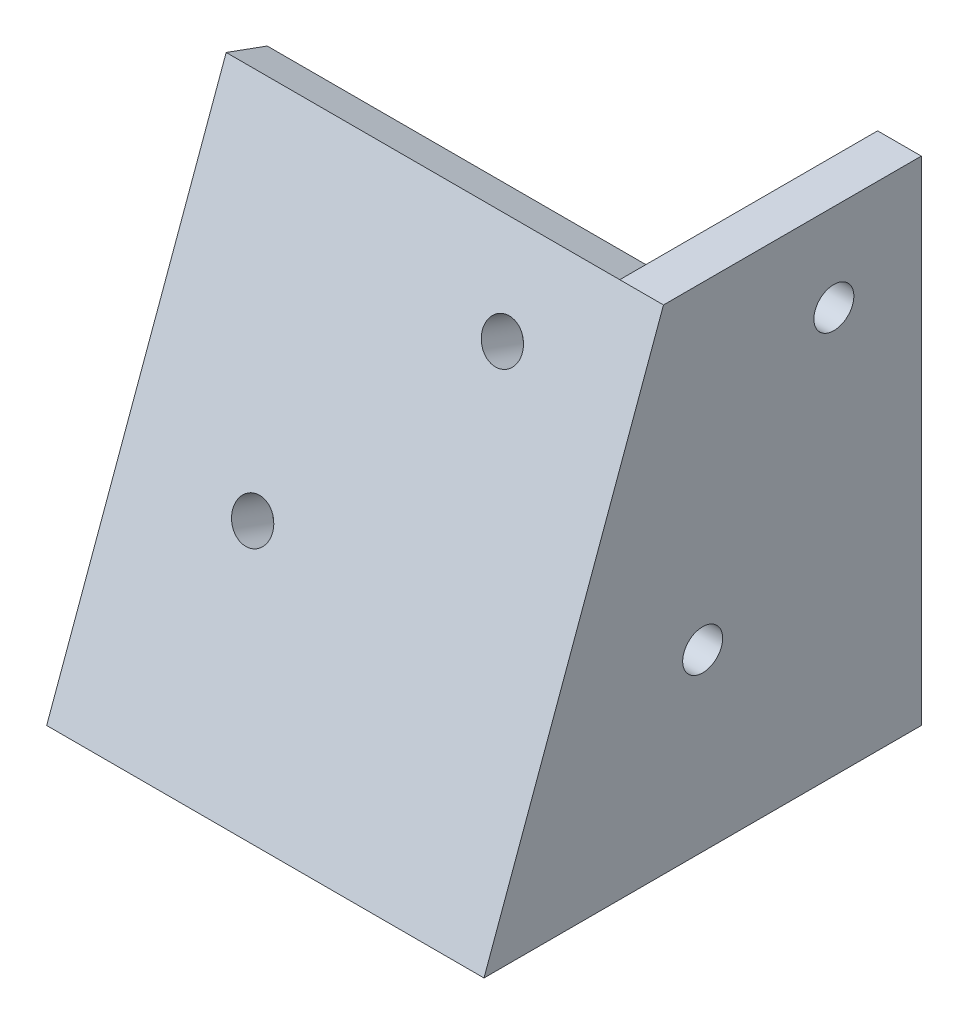
SolidWorks part; units mm, degrees
material "ABS"
ref_plane "Front Plane" through (0, 0, 0) normal (0, 0, 1) x (1, 0, 0)
ref_plane "Top Plane" through (0, 0, 0) normal (0, 1, 0) x (1, 0, 0)
ref_plane "Right Plane" through (0, 0, 0) normal (1, 0, 0) x (0, 0, -1)
sketch "Sketch1" plane through (0, 0, 0) normal (1, 0, 0) x (0, 0, -1)
  line L0 (0, 0) -> (-50, 0)
  line L1 (-50, 0) -> (-29.4788, 56.3816)
  line L2 (-29.4788, 56.3816) -> (-24.7803, 54.6715)
  line L3 (-24.7803, 54.6715) -> (-42.8593, 5)
  line L4 (-42.8593, 5) -> (0, 5)
  line L5 (0, 5) -> (0, 0)
  dimension "D1" = 60
  dimension "D2" = 50
  dimension "D3" = 70
  dimension "D4" = 5
  dimension "D5" = 5
extrude "Main" add sketch "Sketch1" along normal mid plane 50
sketch "Sketch2" plane through (0, 0, 0) normal (0, 0, -1) x (-1, 0, 0)
  line L0 (-25, 56.3816) -> (25, 56.3816) construction
  line L1 (-25, 0) -> (-20, 0)
  line L2 (-25, 0) -> (-25, 56.3816)
  line L3 (-25, 56.3816) -> (-20, 56.3816)
  line L4 (-20, 0) -> (-20, 56.3816)
  point P7 (0, 0)
  dimension "D1" = 5
extrude "Back" add sketch "Sketch2" against normal up to next
hole_wizard "Base Holes" positions "3DSketch4" profile "Sketch5" hole size "#8" standard "ANSI Inch"
sketch3d "3DSketch4"
  line L0 (-25, 5, 0) -> (-25, 5, 42.8593) construction
  line L3 (20, 5, 0) -> (-25, 5, 0) construction
  point P0 (10, 5, 20)
  point P2 (-10, 5, 20)
  dimension "D1" = 15
  dimension "D2" = 15
  dimension "D3" = 20
  dimension "D4" = 20
sketch "Sketch5" plane through (10, 5, 20) normal (1, 0, 0) x (0, 0, 1)
  line L0 (0, 0) -> (0, 5)
  line L1 (0, 5) -> (2.286, 5)
  line L2 (2.286, 5) -> (2.286, 0)
  line L5 (2.286, 0) -> (0, 0)
  line L10 (0, 5) -> (-2.286, 5) construction
  line L11 (0, -6.35) -> (0, 107.95) construction
  dimension "Hole Dia." = 4.572
  dimension "Hole Depth" = 5
  dimension "Drill Angle" = 180
hole_wizard "BackPanelHoles" positions "Sketch6" profile "Sketch7" hole size "#8" standard "ANSI Inch"
sketch "Sketch6" plane through (20, 0, 0) normal (-1, 0, 0) x (0, 0, 1)
  line L0 (29.4788, 56.3816) -> (0, 56.3816) construction
  line L1 (0, 5) -> (0, 56.3816) construction
  line L2 (50, 0) -> (0, 0) construction
  point P0 (10, 46.3816)
  point P2 (25, 20)
  dimension "D1" = 10
  dimension "D2" = 10
  dimension "D3" = 20
  dimension "D4" = 25
sketch "Sketch7" plane through (20, 46.3816, 10) normal (0, 1, 0) x (0, 0, 1)
  line L0 (0, 0) -> (0, 5)
  line L1 (0, 5) -> (2.286, 5)
  line L2 (2.286, 5) -> (2.286, 0)
  line L5 (2.286, 0) -> (0, 0)
  line L10 (0, 5) -> (-2.286, 5) construction
  line L11 (0, -6.35) -> (0, 107.95) construction
  dimension "Hole Dia." = 4.572
  dimension "Hole Depth" = 5
  dimension "Drill Angle" = 180
hole_wizard "SidePanelHoles" positions "3DSketch5" profile "Sketch8" hole size "#8" standard "ANSI Inch"
sketch3d "3DSketch5"
  line L0 (25, 56.3816, 29.4788) -> (25, 0, 50) construction
  line L1 (20, 56.3816, 29.4788) -> (-25, 56.3816, 29.4788) construction
  line L2 (25, 0, 50) -> (-25, 0, 50) construction
  line L3 (-25, 56.3816, 29.4788) -> (-25, 0, 50) construction
  point P0 (10, 46.9846, 32.899)
  point P2 (-10, 23.4923, 41.4495)
  dimension "D1" = 15
  dimension "D2" = 10
  dimension "D3" = 25
  dimension "D4" = 15
  dimension "D5" = 50
  dimension "D6" = 35
sketch "Sketch8" plane through (10, 46.9846, 32.899) normal (1, 0, 0) x (0, -0.9397, 0.342)
  line L0 (0, 0) -> (0, 5)
  line L1 (0, 5) -> (2.286, 5)
  line L2 (2.286, 5) -> (2.286, 0)
  line L5 (2.286, 0) -> (0, 0)
  line L10 (0, 5) -> (-2.286, 5) construction
  line L11 (0, -6.35) -> (0, 107.95) construction
  dimension "Hole Dia." = 4.572
  dimension "Hole Depth" = 5
  dimension "Drill Angle" = 180
ref_plane "Midplane" through (0, 0, 0) normal (-1, 0, 0) x (0, 0, 1)
